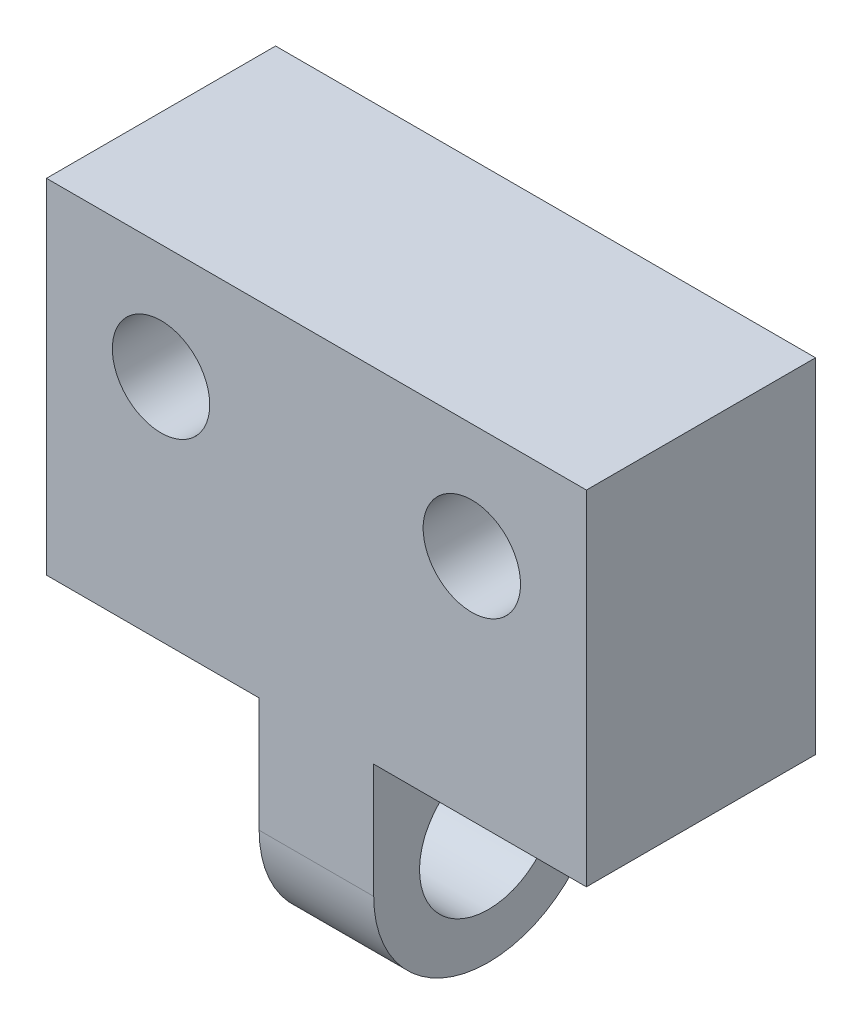
SolidWorks part; units mm, degrees
ref_plane "Front Plane" through (0, 0, 0) normal (0, 0, 1) x (1, 0, 0)
ref_plane "Top Plane" through (0, 0, 0) normal (0, 1, 0) x (1, 0, 0)
ref_plane "Right Plane" through (0, 0, 0) normal (1, 0, 0) x (0, 0, -1)
sketch "Sketch1" plane through (0, 0, 0) normal (0, 0, 1) x (1, 0, 0)
  line L0 (0, 12.1575) -> (18.5649, 12.1575)
  line L1 (18.5649, -7.8425) -> (28.5649, -7.8425)
  line L2 (0, 12.1575) -> (0, 42.1575)
  line L3 (0, 42.1575) -> (47.1297, 42.1575)
  line L4 (47.1297, 12.1575) -> (47.1297, 42.1575)
  line L5 (18.5649, 12.1575) -> (18.5649, -7.8425)
  line L6 (47.1297, 12.1575) -> (28.5649, 12.1575)
  line L7 (28.5649, 12.1575) -> (28.5649, -7.8425)
  dimension "D1" = 50
  dimension "D2" = 10
  dimension "D3" = 18.5649
  dimension "D4" = 18.5649
  dimension "D5" = 47.1297
  dimension "D6" = 20
extrude "Extrude1" add sketch "Sketch1" along normal blind 20
hole_wizard "Ø12.0 (12) Diameter Hole1" positions "3DSketch1" profile "Sketch2" hole size "Ø12.0" standard "Ansi Metric"
sketch3d "3DSketch1"
  line L0 (47.1297, 12.1575, 0) -> (47.1297, 42.1575, 0) construction
  line L1 (47.1297, -7.8425, 20) -> (47.1297, -7.8425, 0) construction
  point P0 (47.1297, 2.1575, 10)
  dimension "D1" = 10
  dimension "D2" = 10
sketch "Sketch2" plane through (47.1297, 2.1575, 10) normal (0, 1, 0) x (0, 0, -1)
  line L0 (0, 0) -> (0, 50.7352)
  line L1 (0, 50.7352) -> (6, 47.13)
  line L2 (6, 47.13) -> (6, 0)
  line L5 (6, 0) -> (0, 0)
  line L10 (0, 50.7352) -> (-6, 47.13) construction
  line L11 (0, -6.35) -> (0, 107.95) construction
  dimension "Hole Dia." = 12
  dimension "Hole Depth" = 47.13
  dimension "Drill Angle" = 118
hole_wizard "Ø8.5 (8.5) Diameter Hole2" positions "3DSketch3" profile "Sketch7" hole size "Ø8.5" standard "Ansi Metric" end condition through all
sketch3d "3DSketch3"
  line L0 (47.1297, 12.1575, 20) -> (47.1297, 42.1575, 20) construction
  line L1 (0, 42.1575, 20) -> (0, 12.1575, 20) construction
  line L2 (47.1297, 42.1575, 20) -> (0, 42.1575, 20) construction
  point P0 (37.1297, 32.1575, 20)
  point P2 (10, 32.1575, 20)
  dimension "D1" = 10
  dimension "D2" = 10
  dimension "D3" = 10
  dimension "D4" = 10
sketch "Sketch7" plane through (37.1297, 32.1575, 20) normal (1, 0, 0) x (0, -1, 0)
  line L0 (0, 0) -> (0, 20)
  line L1 (0, 20) -> (4.25, 20)
  line L2 (4.25, 20) -> (4.25, 0)
  line L5 (4.25, 0) -> (0, 0)
  line L11 (0, -6.35) -> (0, 107.95) construction
  dimension "Thru Hole Dia." = 8.5
  dimension "Thru Hole Depth" = 20
fillet "Fillet1" radius 10 2 edges at (23.5649, -7.8425, 20) (23.5649, -7.8425, 0)
equation "\"D1@3DSketch1\" = \"D1@Extrude1\" / 2"
equation "\"D4@Sketch1\" =  ( \"D5@Sketch1\" - \"D2@Sketch1\" )  / 2"
equation "\"D3@Sketch1\" = \"D4@Sketch1\""
